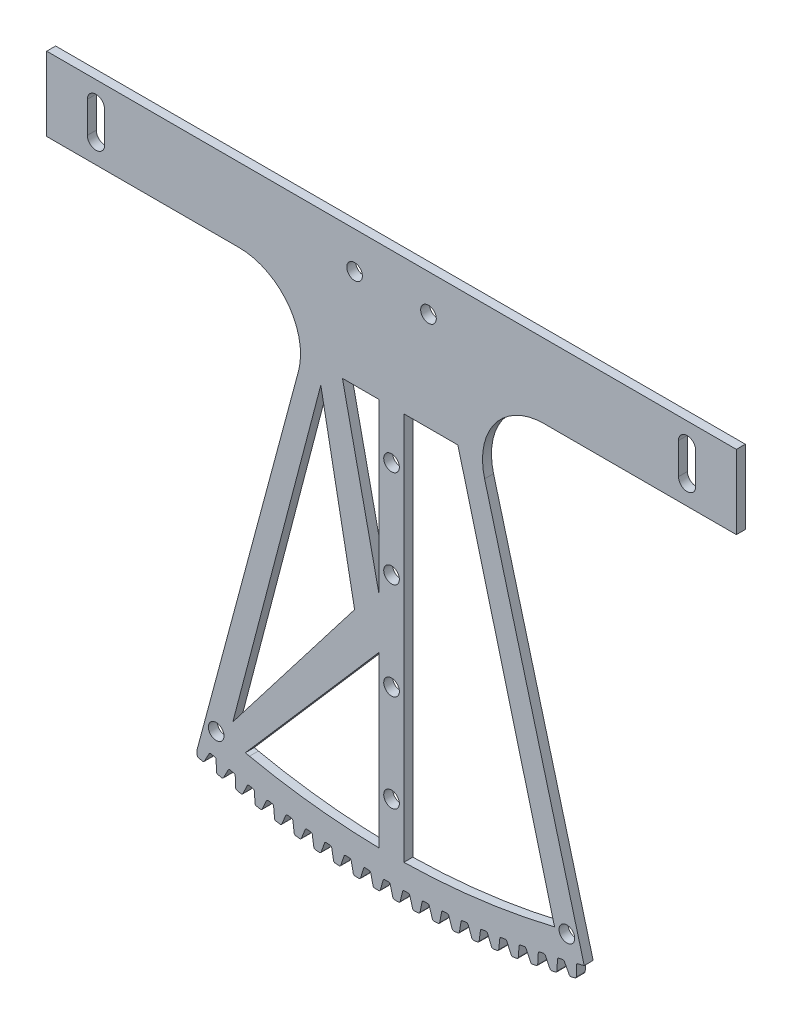
SolidWorks part; units mm, degrees
material "Maple"
ref_plane "Front Plane" through (0, 0, 0) normal (0, 0, 1) x (1, 0, 0)
ref_plane "Top Plane" through (0, 0, 0) normal (0, 1, 0) x (1, 0, 0)
ref_plane "Right Plane" through (0, 0, 0) normal (1, 0, 0) x (0, 0, -1)
sketch "Sketch3" plane through (0, 0, 0) normal (0, 0, 1) x (1, 0, 0)
  line L0 (0, 0) -> (0, -304.8) construction
  line L1 (-21.234, -79.2464) -> (-78.888, -294.4142)
  line L2 (21.234, -79.2464) -> (78.888, -294.4142)
  line L4 (-140, -79.56) -> (140, -79.56)
  line L5 (-140, -79.56) -> (-140, -109.56)
  line L6 (-140, -109.56) -> (140, -109.56)
  line L7 (140, -79.56) -> (140, -109.56)
  line L8 (0, -109.56) -> (0, -79.56) construction
  line L9 (-140, -94.56) -> (140, -94.56) construction
  arc A0 (-78.888, -294.4142) -> (78.888, -294.4142) centre (0, 0) ccw
  point P269 (0, -94.56)
  dimension "D1" = 304.8
  dimension "D4" = 79.56
  dimension "D5" = 30
  dimension "D6" = 280
  dimension "D7" = 140
extrude "Boss-Extrude2" add sketch "Sketch3" along normal blind 3.6286 contours L7 L4 L2 L6 | L1 L6 L2 L4 | L1 L4 L2 | L5 L6 L1 L4 | L1 A0 L2 L6 region at (0, -95.3531, 0) region at (-82.6452, -94.3847, 0) region at (0, -220.3694, 0) region at (82.6452, -94.3847, 0)
fillet "Fillet1" radius 25 2 edges at (-29.3565, -109.56, 1.8143) (29.3565, -109.56, 1.8143)
sketch "Sketch4" plane through (0, -79.56, 0) normal (0, 1, 0) x (1, 0, 0)
  line L1 (-140, 0) -> (140, 0)
  line L2 (-140, 0) -> (-140, -3.6286)
  line L3 (-140, -3.6286) -> (140, -3.6286)
  line L4 (140, 0) -> (140, -3.6286)
  line L5 (0, -3.6286) -> (0, 0) construction
  line L6 (-140, -1.8143) -> (140, -1.8143) construction
  point P252 (0, -1.8143)
sketch "Sketch5" plane through (0, 0, 0) normal (0, 0, -1) x (-1, 0, 0)
  line L0 (-123.5, -94.56) -> (-123.5, -100.91)
  line L1 (-116.5, -94.56) -> (-116.5, -100.91)
  line L2 (116.5, -94.56) -> (116.5, -88.21)
  line L3 (140, -79.56) -> (-140, -79.56) construction
  line L4 (-120, -88.21) -> (-120, -100.91) construction
  line L5 (0, -79.56) -> (0, -109.56) construction
  line L6 (-116.5, -94.56) -> (-116.5, -88.21)
  line L7 (-123.5, -94.56) -> (-123.5, -88.21)
  line L8 (116.5, -94.56) -> (116.5, -100.91)
  line L9 (123.5, -94.56) -> (123.5, -100.91)
  line L10 (123.5, -94.56) -> (123.5, -88.21)
  line L11 (-140, -79.56) -> (-140, -109.56) construction
  line L12 (120, -88.21) -> (120, -100.91) construction
  arc A1 (-116.5, -88.21) -> (-123.5, -88.21) centre (-120, -88.21) ccw
  arc A2 (-123.5, -100.91) -> (-116.5, -100.91) centre (-120, -100.91) ccw
  arc A3 (123.5, -100.91) -> (116.5, -100.91) centre (120, -100.91) cw
  arc A4 (116.5, -88.21) -> (123.5, -88.21) centre (120, -88.21) cw
  circle A5 centre (-15, -94.56) radius 3.175
  circle A6 centre (15, -94.56) radius 3.175
  dimension "D1" = 16.5
  dimension "D2" = 7
  dimension "D3" = 8.65
  dimension "D5" = 3.5
  dimension "D6" = 15
  dimension "D8" = 6.35
  dimension "D4" = 6.35
  dimension "D7" = 15
sketch "Sketch13" plane through (0, 0, 0) normal (0, 0, -1) x (-1, 0, 0)
  line L0 (0, 0) -> (78.888, -294.4142)
  line L1 (0, 0) -> (-78.888, -294.4142)
  arc A0 (-78.888, -294.4142) -> (78.888, -294.4142) centre (0, 0) ccw
  arc A1 (-78.888, -294.4142) -> (78.888, -294.4142) centre (0, 0) ccw construction
  arc A2 (-78.888, -294.4142) -> (78.888, -294.4142) centre (0, 0) ccw
  circle A3 centre (0, 0) radius 304.8
  dimension "D1" = 609.6
sketch "Sketch14" plane through (0, 0, 0) normal (0, 0, -1) x (-1, 0, 0)
  line L0 (0, 0) -> (80.0203, -298.6399) construction
  line L2 (78.888, -294.4142) -> (78.9109, -297.0369)
  line L3 (78.9109, -297.0369) -> (76.2891, -297.7211)
  line L18 (76.2891, -297.7211) -> (75.0275, -295.4216)
  line L20 (0, 0) -> (-79.2746, -295.8555) construction
  line L32 (78.888, -294.4142) -> (75.0275, -295.4216)
  line L33 (75.0275, -295.4216) -> (78.888, -294.4142)
  line L34 (0, 0) -> (-75.3952, -296.8678) construction
  line L35 (0, 0) -> (-71.5028, -297.8293) construction
  line L36 (0, 0) -> (-67.5982, -298.7397) construction
  line L37 (0, 0) -> (-63.6821, -299.5989) construction
  line L38 (0, 0) -> (-59.755, -300.4068) construction
  line L39 (0, 0) -> (-55.8176, -301.1633) construction
  line L40 (0, 0) -> (-51.8707, -301.8681) construction
  line L41 (0, 0) -> (-47.9149, -302.5212) construction
  line L42 (0, 0) -> (-43.951, -303.1225) construction
  line L43 (0, 0) -> (-39.9794, -303.6718) construction
  line L44 (0, 0) -> (-36.0011, -304.1691) construction
  line L45 (0, 0) -> (-32.0165, -304.6143) construction
  line L46 (0, 0) -> (-28.0265, -305.0073) construction
  line L47 (0, 0) -> (-24.0316, -305.348) construction
  line L48 (0, 0) -> (-20.0327, -305.6364) construction
  line L49 (0, 0) -> (-16.0303, -305.8724) construction
  line L50 (0, 0) -> (-12.0252, -306.0561) construction
  line L51 (0, 0) -> (-8.018, -306.1873) construction
  line L52 (0, 0) -> (-4.0094, -306.266) construction
  line L53 (0, 0) -> (-0.0002, -306.2922) construction
  line L54 (0, 0) -> (4.0091, -306.266) construction
  line L55 (0, 0) -> (8.0176, -306.1873) construction
  line L56 (0, 0) -> (12.0248, -306.0561) construction
  line L57 (0, 0) -> (16.03, -305.8725) construction
  line L58 (0, 0) -> (20.0323, -305.6364) construction
  line L59 (0, 0) -> (24.0313, -305.348) construction
  line L60 (0, 0) -> (28.0261, -305.0073) construction
  line L61 (0, 0) -> (32.0162, -304.6143) construction
  line L62 (0, 0) -> (36.0007, -304.1691) construction
  line L63 (0, 0) -> (39.9791, -303.6719) construction
  line L64 (0, 0) -> (43.9506, -303.1225) construction
  line L65 (0, 0) -> (47.9146, -302.5213) construction
  line L66 (0, 0) -> (51.8704, -301.8682) construction
  line L67 (0, 0) -> (55.8173, -301.1633) construction
  line L68 (0, 0) -> (59.7546, -300.4069) construction
  line L69 (0, 0) -> (63.6817, -299.599) construction
  line L70 (0, 0) -> (67.5979, -298.7398) construction
  line L71 (0, 0) -> (71.5025, -297.8293) construction
  line L72 (0, 0) -> (75.3948, -296.8679) construction
  line L73 (0, 0) -> (-79.2746, -295.8555) construction
  line L74 (0, 0) -> (-75.3952, -296.8678) construction
  line L137 (37.789, -141.0305) -> (78.888, -294.4142) construction
  line L138 (-140, -79.56) -> (-140, -109.56)
  line L139 (-140, -109.56) -> (-61.9371, -109.56)
  line L140 (-37.789, -141.0305) -> (-78.888, -294.4142)
  line L141 (78.888, -294.4142) -> (37.789, -141.0305)
  line L142 (61.9371, -109.56) -> (140, -109.56)
  line L143 (140, -109.56) -> (140, -79.56)
  line L144 (140, -79.56) -> (-140, -79.56)
  line L145 (-140, -79.56) -> (-140, -109.56)
  line L146 (-140, -109.56) -> (-61.9371, -109.56)
  line L147 (-37.789, -141.0305) -> (-78.888, -294.4142)
  line L149 (61.9371, -109.56) -> (140, -109.56)
  line L150 (140, -109.56) -> (140, -79.56)
  line L151 (140, -79.56) -> (-140, -79.56)
  circle A0 centre (0, 0) radius 307.34
  circle A1 centre (0, 0) radius 302.26
  arc A3 (-37.789, -141.0305) -> (-61.9371, -109.56) centre (-61.9371, -134.56) ccw
  arc A5 (61.9371, -109.56) -> (37.789, -141.0305) centre (61.9371, -134.56) ccw
  arc A6 (-37.789, -141.0305) -> (-61.9371, -109.56) centre (-61.9371, -134.56) ccw
  arc A8 (61.9371, -109.56) -> (37.789, -141.0305) centre (61.9371, -134.56) ccw
  arc A11 (-78.888, -294.4142) -> (78.888, -294.4142) centre (0, 0) ccw
  arc A12 (-78.888, -294.4142) -> (78.888, -294.4142) centre (0, 0) ccw
  arc M181 (-78.888, -294.4142) -> (78.888, -294.4142) centre (0, 0) ccw
  dimension "D5" = 614.68
  dimension "D6" = 30
  dimension "D7" = 40
  dimension "D4" = 604.52
  dimension "D1" = 14.5
  dimension "D3" = 14.5
  dimension "D8" = 0.75
  dimension "D9" = 306.2922
  dimension "D10" = 0.75
  dimension "D2" = 0
extrude "Boss-Extrude4" add sketch "Sketch14" against normal up to surface (3.6286 mm away) contours L2 M181 region at (-77.2591, -296.0724, 0) up to face at (0, -146.6727, 3.6286)
sketch "Sketch15" plane through (0, 0, 0) normal (1, 0, 0) x (0, 0, -1)
  line L0 (0, 0) -> (-23.3364, 0) construction
sketch "Sketch16" plane through (0, 0, 0) normal (0, 0, -1) x (-1, 0, 0)
  line L0 (75.0275, -295.4216) -> (73.7653, -293.1208)
  line L1 (73.7653, -293.1208) -> (71.1999, -293.7544)
  line L2 (71.1999, -293.7544) -> (71.1541, -296.3784)
  line L3 (0, 0) -> (71.5025, -297.8293) construction
  line L4 (0, 0) -> (75.3948, -296.8679) construction
  circle A0 centre (0, 0) radius 302.26 construction
  arc A1 (-78.888, -294.4142) -> (78.888, -294.4142) centre (0, 0) ccw construction
  dimension "D1" = 14.5
  dimension "D2" = 14.5
extrude "Cut-Extrude2" cut sketch "Sketch16" against normal through all and the other way through all
fillet "Fillet2" radius 0.7 2 edges at (-76.2891, -297.7211, 1.8143) (-78.9109, -297.0369, 1.8143)
pattern_circular "CirPattern8" count 20 every 1.5 about axis through (0, 0, 0) along (0, 0, 1) of "Cut-Extrude2", "Boss-Extrude4", "Fillet2"
extrude "Cut-Extrude3" cut sketch "Sketch5" against normal through all
sketch "Sketch17" plane through (0, 0, 0) normal (0, 0, -1) x (-1, 0, 0)
  line L0 (0, -79.56) -> (0, -134.56) construction
  line L1 (140, -79.56) -> (-140, -79.56) construction
  line L2 (-61.9371, -109.56) -> (61.9371, -109.56) construction
  line L3 (-36.9371, -134.56) -> (-26.9371, -134.56) construction
  line L4 (-36.9371, -134.56) -> (-26.9371, -134.56) construction
  line L5 (-26.9371, -134.56) -> (-66.1944, -284.3612) construction
  line L6 (-66.1944, -284.3612) -> (-76.1944, -284.3612) construction
  line L7 (0, -292.2593) -> (5, -292.2593) construction
  line L8 (-37.789, -141.0305) -> (-78.888, -294.4142) construction
  line L9 (0, -134.56) -> (-5, -134.56) construction
  line L10 (0, -134.56) -> (5, -134.56) construction
  line L11 (26.9371, -134.56) -> (36.9371, -134.56) construction
  line L12 (-5, -134.56) -> (-5, -292.2593) construction
  line L13 (36.9371, -134.56) -> (26.9371, -134.56) construction
  line L14 (26.9371, -134.56) -> (66.1944, -284.3612) construction
  line L15 (66.1944, -284.3612) -> (76.1944, -284.3612) construction
  line L16 (37.789, -141.0305) -> (78.888, -294.4142) construction
  line L17 (0.6571, -302.2593) -> (-3.5916, -302.2593) construction
  line L18 (-5, -134.56) -> (5, -134.56) construction
  line L19 (-3.5916, -292.2593) -> (-5, -292.2593) construction
  line L20 (5, -134.56) -> (5, -292.2593) construction
  line L21 (-3.5916, -302.2593) -> (-3.5916, -292.2593) construction
  line L22 (0, -193.6972) -> (0, -233.1221) construction
  line L23 (64.4199, -277.5899) -> (15, -213.4096)
  line L24 (-66.1944, -284.3612) -> (-68.6354, -294.3612) construction
  line L25 (-67.3487, -294.6613) -> (-69.9221, -294.0612) construction
  line L26 (71.1999, -293.7544) -> (66.067, -294.9513) construction
  line L27 (66.1944, -284.3612) -> (68.6335, -294.3529) construction
  line L28 (26.9371, -134.56) -> (66.1944, -284.3612)
  line L29 (26.9371, -134.56) -> (5, -134.56)
  line L30 (5, -134.56) -> (5, -292.2593)
  line L31 (-66.1944, -284.3612) -> (-26.9371, -134.56)
  line L32 (-26.9371, -134.56) -> (-5, -134.56)
  line L33 (-5, -134.56) -> (-5, -292.2593)
  line L34 (15, -213.4096) -> (28.7117, -141.3313)
  line L35 (66.1944, -284.3612) -> (57.6779, -286.2946)
  line L36 (66.1944, -284.3612) -> (64.4199, -277.5899) construction
  line L37 (5, -223.4096) -> (59.3729, -285.9321)
  line L41 (26.9371, -134.56) -> (28.7117, -141.3313) construction
  line L42 (26.9371, -134.56) -> (19.9371, -134.56) construction
  line L44 (28.7117, -141.3313) -> (26.9371, -134.56) construction
  line L47 (5, -203.4096) -> (19.9371, -134.56)
  circle A0 centre (0, -272.5469) radius 3.175
  arc A1 (61.9371, -109.56) -> (37.789, -141.0305) centre (61.9371, -134.56) ccw construction
  arc A2 (-37.789, -141.0305) -> (-61.9371, -109.56) centre (-61.9371, -134.56) ccw construction
  arc A3 (-66.1944, -284.3612) -> (-5, -292.2593) centre (0, -12.5018) ccw
  arc A4 (5, -292.2593) -> (66.1944, -284.3612) centre (0, -12.5018) ccw
  circle A5 centre (0, -233.1221) radius 3.175
  circle A6 centre (0, -193.6972) radius 3.175
  circle A7 centre (0, -154.2724) radius 3.175
  circle A8 centre (-71.1944, -284.3612) radius 3.175
  circle A9 centre (71.1944, -284.3612) radius 3.175
  arc A13 (19.9371, -134.56) -> (28.7117, -141.3313) centre (26.9371, -134.56) ccw construction
  arc A14 (19.9371, -134.56) -> (28.7117, -141.3313) centre (26.9371, -134.56) ccw construction
  arc A15 (-59.3729, -285.9321) -> (-64.4199, -277.5899) centre (-66.1944, -284.3612) ccw construction
  arc A16 (-64.4199, -277.5899) -> (-59.3729, -285.9321) centre (-66.1944, -284.3612) cw
  arc A17 (-5, -203.4096) -> (-5, -223.4096) centre (-5, -213.4096) ccw construction
  arc A18 (-28.7117, -141.3313) -> (-19.9371, -134.56) centre (-26.9371, -134.56) ccw construction
  arc A19 (5, -223.4096) -> (5, -203.4096) centre (5, -213.4096) ccw construction
  arc A20 (64.4199, -277.5899) -> (59.3729, -285.9321) centre (66.1944, -284.3612) ccw construction
  dimension "D13" = 6.35
  dimension "D14" = 6.35
  dimension "D15" = 10
  dimension "D16" = 7
  dimension "D17" = 7
  dimension "D20" = 7
  dimension "D21" = 10
  dimension "D22" = 7
  dimension "D18" = 7
  dimension "D1" = 10
  dimension "D2" = 5
  dimension "D3" = 10
  dimension "D4" = 10
  dimension "D5" = 5
  dimension "D6" = 5
  dimension "D7" = 10
  dimension "D8" = 10
  dimension "D9" = 5
  dimension "D10" = 10
  dimension "D11" = 157.6993
  dimension "D12" = 10
extrude "Cut-Extrude4" cut sketch "Sketch17" against normal through all contours L31 | L34 L23 L28 | L30 A4 L35 L37 | A3 L33 | L30 L47 L29 | L33 L32 | A6 | A7 | A5 | A0 | A9 | A8 region at (-36.0438, -210.777, 0) region at (-23.3567, -267.7722, 0) region at (-9.979, -157.5099, 0) region at (62.5855, -282.1856, 0) region at (27.141, -224.0716, 0) region at (0, -272.5469, 0) region at (0, -233.1221, 0) region at (0, -193.6972, 0) region at (0, -154.2724, 0) region at (71.1944, -284.3612, 0) region at (-71.1944, -284.3612, 0)
fillet "Fillet3" radius 0.7 39 edges at (75.039, -292.7973, 1.8143) (69.9221, -294.0612, 1.8143) (67.3487, -294.6613, 1.8143) (62.2005, -295.7908, 1.8143) (59.6123, -296.3233, 1.8143) (54.4363, -297.3177, 1.8143) (51.835, -297.7822, 1.8143) (46.6348, -298.6408, 1.8143) (44.0223, -299.037, 1.8143) (38.8013, -299.7592, 1.8143) (36.1793, -300.0869, 1.8143) (30.9412, -300.6722, 1.8143) (28.3115, -300.9312, 1.8143) (23.06, -301.3791, 1.8143) (20.4244, -301.5692, 1.8143) (15.1629, -301.8794, 1.8143) (12.5232, -302.0005, 1.8143) (7.2554, -302.1729, 1.8143) (4.6135, -302.2248, 1.8143) (-0.6571, -302.2593, 1.8143) (-3.2994, -302.242, 1.8143) (-8.5691, -302.1385, 1.8143) (-11.2101, -302.0521, 1.8143) (-16.4752, -301.8107, 1.8143) (-19.113, -301.6551, 1.8143) (-24.37, -301.276, 1.8143) (-27.0029, -301.0514, 1.8143) (-32.2482, -300.5348, 1.8143) (-34.8743, -300.2414, 1.8143) (-40.1042, -299.5877, 1.8143) (-42.7217, -299.2256, 1.8143) (-47.9327, -298.4352, 1.8143) (-50.5399, -298.0047, 1.8143) (-55.7284, -297.0782, 1.8143) (-58.3234, -296.5796, 1.8143) (-63.4859, -295.5176, 1.8143) (-66.067, -294.9513, 1.8143) (-71.1999, -293.7544, 1.8143) (-73.7653, -293.1208, 1.8143)
sketch "Sketch18" plane through (0, 0, 3.6286) normal (0, 0, 1) x (1, 0, 0)
  line L0 (37.789, -141.0305) -> (78.8881, -294.4142) construction
  line L1 (78.2307, -291.9607) -> (79.7629, -294.7684)
  line L2 (79.7629, -294.7684) -> (77.5958, -294.9491)
  line L3 (77.5958, -294.9491) -> (77.5958, -292.1301)
  arc A0 (77.5958, -292.1301) -> (78.2307, -291.9607) centre (0, 0) ccw
extrude "Cut-Extrude5" cut sketch "Sketch18" against normal blind 10
equation "\"D7@Sketch3\"=\"D6@Sketch3\"/2"
